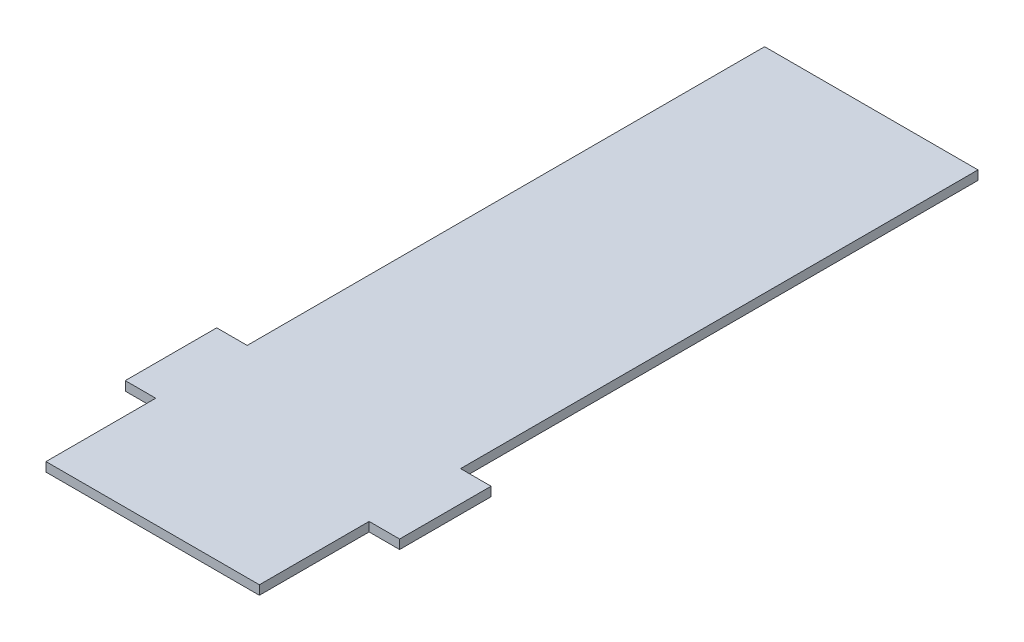
SolidWorks part; units mm, degrees
ref_plane "Front Plane" through (0, 0, 0) normal (0, 0, 1) x (1, 0, 0)
ref_plane "Top Plane" through (0, 0, 0) normal (0, 1, 0) x (1, 0, 0)
ref_plane "Right Plane" through (0, 0, 0) normal (1, 0, 0) x (0, 0, -1)
sketch "Sketch5" plane through (0, 0, 0) normal (0, 1, 0) x (1, 0, 0)
  line L0 (70, 36) -> (80, 36)
  line L1 (0, 0) -> (70, 0)
  line L2 (0, 0) -> (0, 235.74)
  line L3 (0, 235.74) -> (70, 235.74)
  line L4 (70, 0) -> (70, 235.74)
  line L5 (80, 36) -> (80, 66)
  line L6 (80, 66) -> (70, 66)
  line L7 (35, 235.74) -> (35, 0) construction
  line L8 (-10, 66) -> (0, 66)
  line L9 (-10, 36) -> (-10, 66)
  line L10 (0, 36) -> (-10, 36)
  dimension "D1" = 235.74
  dimension "D2" = 70
  dimension "D3" = 36
  dimension "D4" = 30
  dimension "D5" = 10
extrude "Boss-Extrude5" add sketch "Sketch5" along normal blind 3 contours L10 L2 L8 L9 | L7 L3 L2 L1 | L3 L7 L1 L4 | L5 L6 L4 L0 region at (75, 0, -51) region at (52.5, 0, -117.87) region at (17.5, 0, -117.87) region at (-5, 0, -51)
